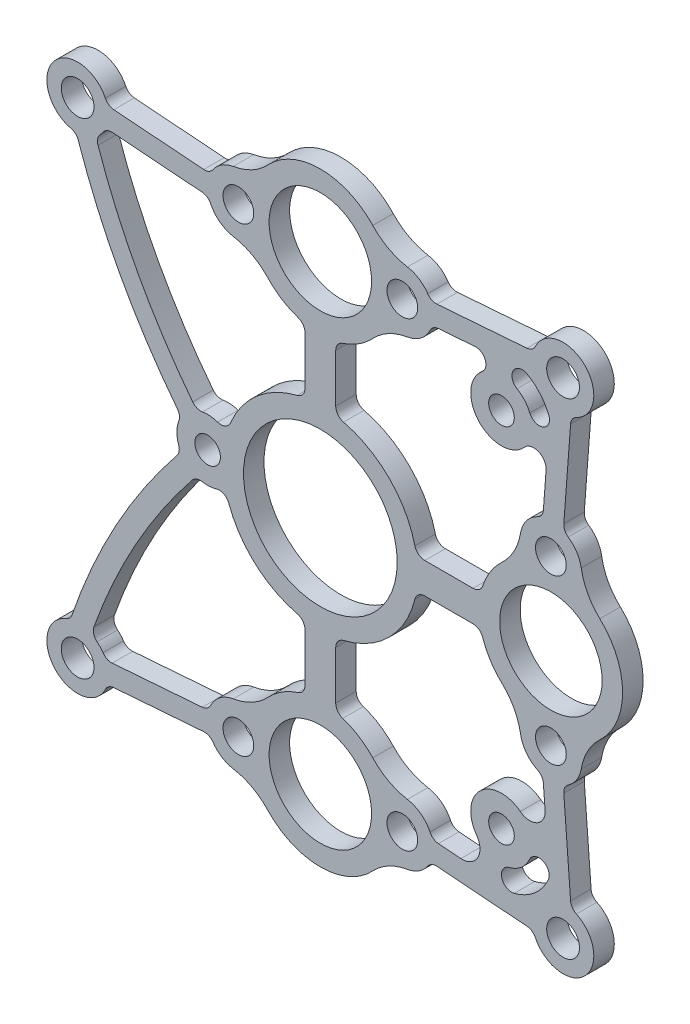
SolidWorks part; units mm, degrees
material "A2017"
ref_plane "正面" through (0, 0, 0) normal (0, 0, 1) x (1, 0, 0)
ref_plane "平面" through (0, 0, 0) normal (0, 1, 0) x (1, 0, 0)
ref_plane "右側面" through (0, 0, 0) normal (1, 0, 0) x (0, 0, -1)
sketch "ｽｹｯﾁ1" plane through (0, 0, 0) normal (0, 0, 1) x (1, 0, 0)
  line L0 (0, 29.5) -> (0, 22.5) construction
  line L1 (-8, 22.5) -> (8, 22.5) construction
  line L2 (29.5, 0) -> (22.5, 0) construction
  line L3 (22.5, 8) -> (22.5, -8) construction
  line L4 (0, -29.5) -> (0, -22.5) construction
  line L5 (8, -22.5) -> (-8, -22.5) construction
  line L6 (-29.5, 0) -> (-22.5, 0) construction
  line L7 (-22.5, -8) -> (-22.5, 8) construction
  circle A1 centre (23.6881, 23.6881) radius 3
  circle A2 centre (23.6881, 23.6881) radius 3
  circle A3 centre (22.5, 0) radius 5
  circle A5 centre (22.5, -8) radius 1.5
  circle A7 centre (0, 22.5) radius 5
  circle A8 centre (0, 22.5) radius 5
  circle A9 centre (0, 0) radius 7.5
  circle A10 centre (0, 0) radius 7.5
  circle A11 centre (8, 22.5) radius 1.5
  circle A12 centre (8, 22.5) radius 1.5
  circle A13 centre (-8, 22.5) radius 1.5
  circle A14 centre (-8, 22.5) radius 1.5
  circle A15 centre (-23.6881, -23.6881) radius 3
  circle A16 centre (-23.6881, -23.6881) radius 3
  circle A17 centre (-23.6881, 23.6881) radius 3
  circle A18 centre (-23.6881, 23.6881) radius 3
  circle A19 centre (23.6881, -23.6881) radius 3
  circle A20 centre (23.6881, -23.6881) radius 3
  circle A21 centre (22.5, 8) radius 1.5
  arc A23 (27.2784, 5.1154) -> (27.2784, -5.1154) centre (22.5, 0) cw
  arc A25 (27.2784, 5.1154) -> (25.458, 8.5) centre (31.3741, 9.5) cw
  arc A27 (27.2784, -5.1154) -> (25.458, -8.5) centre (31.3741, -9.5) ccw
  circle A42 centre (0, 0) radius 9.5
  circle A43 centre (-23.6881, 23.6881) radius 1.6
  circle A44 centre (-23.6881, -23.6881) radius 1.6
  circle A45 centre (23.6881, -23.6881) radius 1.6
  circle A46 centre (23.6881, 23.6881) radius 1.6
  circle A47 centre (-8, 22.5) radius 3 construction
  circle A48 centre (0, 22.5) radius 7 construction
  circle A49 centre (8, 22.5) radius 3 construction
  arc A50 (-5.1154, 27.2784) -> (5.1154, 27.2784) centre (0, 22.5) cw
  arc A51 (-5.1154, 27.2784) -> (-8.5, 25.458) centre (-9.5, 31.3741) cw
  arc A52 (5.1154, 27.2784) -> (8.5, 25.458) centre (9.5, 31.3741) ccw
  arc A53 (-8.5, 25.458) -> (-8.5, 19.542) centre (-8, 22.5) ccw
  arc A54 (8.5, 25.458) -> (8.5, 19.542) centre (8, 22.5) cw
  arc A55 (-5.1154, 17.7216) -> (-8.5, 19.542) centre (-9.5, 13.6259) ccw
  arc A56 (-5.1154, 17.7216) -> (5.1154, 17.7216) centre (0, 22.5) ccw
  arc A57 (5.1154, 17.7216) -> (8.5, 19.542) centre (9.5, 13.6259) cw
  arc A58 (25.458, 8.5) -> (19.542, 8.5) centre (22.5, 8) ccw
  arc A59 (25.458, -8.5) -> (19.542, -8.5) centre (22.5, -8) cw
  arc A60 (17.7216, 5.1154) -> (19.542, 8.5) centre (13.6259, 9.5) ccw
  arc A61 (17.7216, 5.1154) -> (17.7216, -5.1154) centre (22.5, 0) ccw
  arc A62 (17.7216, -5.1154) -> (19.542, -8.5) centre (13.6259, -9.5) cw
  circle A63 centre (22.5, 8) radius 3 construction
  circle A64 centre (22.5, 0) radius 7 construction
  circle A65 centre (22.5, -8) radius 3 construction
  circle A66 centre (0, -22.5) radius 5
  circle A67 centre (-8, -22.5) radius 1.5
  circle A68 centre (8, -22.5) radius 1.5
  arc A69 (5.1154, -27.2784) -> (-5.1154, -27.2784) centre (0, -22.5) cw
  arc A70 (5.1154, -27.2784) -> (8.5, -25.458) centre (9.5, -31.3741) cw
  arc A71 (-5.1154, -27.2784) -> (-8.5, -25.458) centre (-9.5, -31.3741) ccw
  arc A72 (8.5, -25.458) -> (8.5, -19.542) centre (8, -22.5) ccw
  arc A73 (-8.5, -25.458) -> (-8.5, -19.542) centre (-8, -22.5) cw
  arc A74 (5.1154, -17.7216) -> (8.5, -19.542) centre (9.5, -13.6259) ccw
  arc A75 (5.1154, -17.7216) -> (-5.1154, -17.7216) centre (0, -22.5) ccw
  arc A76 (-5.1154, -17.7216) -> (-8.5, -19.542) centre (-9.5, -13.6259) cw
  circle A77 centre (8, -22.5) radius 3 construction
  circle A78 centre (0, -22.5) radius 7 construction
  circle A79 centre (-8, -22.5) radius 3 construction
  circle A80 centre (-22.5, 0) radius 5 [skipped]
  circle A81 centre (-22.5, 8) radius 1.5 [skipped]
  circle A82 centre (-22.5, -8) radius 1.5 [skipped]
  arc A83 (-27.2784, -5.1154) -> (-27.2784, 5.1154) centre (-22.5, 0) cw [skipped]
  arc A84 (-27.2784, -5.1154) -> (-25.458, -8.5) centre (-31.3741, -9.5) cw [skipped]
  arc A85 (-27.2784, 5.1154) -> (-25.458, 8.5) centre (-31.3741, 9.5) ccw [skipped]
  arc A86 (-25.458, -8.5) -> (-19.542, -8.5) centre (-22.5, -8) ccw [skipped]
  arc A87 (-25.458, 8.5) -> (-19.542, 8.5) centre (-22.5, 8) cw [skipped]
  arc A88 (-17.7216, -5.1154) -> (-19.542, -8.5) centre (-13.6259, -9.5) ccw [skipped]
  arc A89 (-17.7216, -5.1154) -> (-17.7216, 5.1154) centre (-22.5, 0) ccw [skipped]
  arc A90 (-17.7216, 5.1154) -> (-19.542, 8.5) centre (-13.6259, 9.5) cw [skipped]
  circle A91 centre (-22.5, -8) radius 3 construction
  circle A92 centre (-22.5, 0) radius 7 construction
  circle A93 centre (-22.5, 8) radius 3 construction
  point P121 (0, 0)
  dimension "D15" = 19
  dimension "D16" = 2
  dimension "D17" = 3.2
  dimension "D18" = 14
  dimension "D19" = 6
  dimension "D20" = 6
  dimension "D1" = 0
  dimension "D3" = 4
  dimension "D4" = 0
  dimension "D5" = 0
  dimension "D6" = 0
  dimension "D7" = 0
  dimension "D8" = 0
  dimension "D9" = 0
  dimension "D10" = 0
extrude "ﾎﾞｽ - 押し出し1" add sketch "ｽｹｯﾁ1" against normal blind 2
sketch "ｽｹｯﾁ2" plane through (0, 0, 0) normal (0, 0, 1) x (1, 0, 0)
  circle A0 centre (-11, 0.25) radius 1.5 construction
  circle A1 centre (17.6777, 17.9277) radius 1.5 construction
  circle A2 centre (17.6777, -17.4277) radius 1.5 construction
  circle A3 centre (-11, 0.25) radius 3
  circle A4 centre (17.6777, 17.9277) radius 3
  circle A5 centre (17.6777, -17.4277) radius 3
  dimension "D1" = 3
  dimension "D2" = 6
extrude "ﾎﾞｽ - 押し出し2" add sketch "ｽｹｯﾁ2" against normal through all
hole_wizard "M3 ねじ穴1" positions "ｽｹｯﾁ3" profile "ｽｹｯﾁ4" tap size "M3" standard "JIS" end condition through all
sketch "ｽｹｯﾁ3" plane through (0, 0, 0) normal (0, 0, 1) x (1, 0, 0)
  point P0 (-11, 0.25)
  point P3 (17.6777, 17.9277)
  point P6 (17.6777, -17.4277)
sketch "ｽｹｯﾁ4" plane through (-11, 0.25, 0) normal (1, 0, 0) x (0, -1, 0)
  line L0 (0, 0) -> (0, 2)
  line L1 (0, 2) -> (1.25, 2)
  line L2 (1.25, 2) -> (1.25, 0)
  line L5 (1.25, 0) -> (0, 0)
  line L11 (0, -6.35) -> (0, 107.95) construction
  dimension "次ｻｰﾌｪｽまでのねじ下穴ﾄﾞﾘﾙ直径" = 2.5
  dimension "次ｻｰﾌｪｽまでのねじ下穴ﾄﾞﾘﾙの深さ" = 2
cosmetic thread "穴のねじ山1" parameters "D2"=3
cosmetic thread "穴のねじ山2" parameters "D2"=3
cosmetic thread "穴のねじ山3" parameters "D2"=3
sketch "ｽｹｯﾁ5" plane through (0, 0, 0) normal (0, 0, 1) x (1, 0, 0)
  line L0 (0, 22.5) -> (0, 0) construction
  line L1 (0, 22.5) -> (0, 0) construction
  line L2 (1.5, 22.5) -> (1.5, 0)
  line L3 (-1.5, 22.5) -> (-1.5, 0)
  line L4 (22.5, 0) -> (0, 0) construction
  line L5 (22.5, -1.5) -> (0, -1.5)
  line L6 (22.5, 1.5) -> (0, 1.5)
  line L7 (0, 0) -> (0, -22.5) construction
  line L8 (1.5, 0) -> (1.5, -22.5)
  line L9 (-1.5, 0) -> (-1.5, -22.5)
  arc A0 (1.5, 22.5) -> (-1.5, 22.5) centre (0, 22.5) ccw
  arc A1 (-1.5, 0) -> (1.5, 0) centre (0, 0) ccw
  arc A2 (22.5, -1.5) -> (22.5, 1.5) centre (22.5, 0) ccw
  arc A3 (0, 1.5) -> (0, -1.5) centre (0, 0) ccw
  arc A4 (1.5, 0) -> (-1.5, 0) centre (0, 0) ccw
  arc A5 (-1.5, -22.5) -> (1.5, -22.5) centre (0, -22.5) ccw
  arc A6 (5.1154, -17.7216) -> (-5.1154, -17.7216) centre (0, -22.5) ccw construction
  arc A7 (17.7216, 5.1154) -> (17.7216, -5.1154) centre (22.5, 0) ccw construction
  arc A8 (-5.1154, 17.7216) -> (5.1154, 17.7216) centre (0, 22.5) ccw construction
  arc A9 (-9.2456, -2.1836) -> (-9.1369, 2.6014) centre (0, 0) ccw construction
  arc A10 (5.1154, -17.7216) -> (-5.1154, -17.7216) centre (0, -22.5) ccw
  arc A11 (17.7216, 5.1154) -> (17.7216, -5.1154) centre (22.5, 0) ccw
  arc A12 (-5.1154, 17.7216) -> (5.1154, 17.7216) centre (0, 22.5) ccw
  arc A13 (-9.2456, -2.1836) -> (-9.1369, 2.6014) centre (0, 0) ccw
  point P4 (0, 11.25)
  point P12 (11.25, 0)
  point P17 (0, -11.25)
  arc M19 (-5.1154, 17.7216) -> (5.1154, 17.7216) centre (0, 22.5) ccw
  dimension "D1" = 3
extrude "ﾎﾞｽ - 押し出し3" add sketch "ｽｹｯﾁ5" against normal through all contours A13 L2 L3 M19 | A13 L5 A11 L6 | A13 L9 A10 L8 region at (0, 12.5073, 0) region at (12.5073, 0, 0) region at (0, -12.5073, 0)
sketch "ｽｹｯﾁ6" plane through (0, 0, 0) normal (0, 0, 1) x (1, 0, 0)
  line L0 (8, 22.5) -> (23.6881, 23.6881) construction
  line L1 (7.9245, 23.4971) -> (23.6126, 24.6852)
  line L2 (8.0755, 21.5029) -> (23.7636, 22.6909)
  line L3 (22.5, 8) -> (23.6881, 23.6881) construction
  line L4 (21.5029, 8.0755) -> (22.6909, 23.7636)
  line L5 (23.4971, 7.9245) -> (24.6852, 23.6126)
  line L6 (0, 0) -> (29.5, 0) construction
  line L7 (8, -22.5) -> (23.6881, -23.6881) construction
  line L8 (7.9245, -23.4971) -> (23.6126, -24.6852)
  line L9 (8.0755, -21.5029) -> (23.7636, -22.6909)
  line L10 (22.5, -8) -> (23.6881, -23.6881) construction
  line L11 (21.5029, -8.0755) -> (22.6909, -23.7636)
  line L12 (23.4971, -7.9245) -> (24.6852, -23.6126)
  arc A0 (7.9245, 23.4971) -> (8.0755, 21.5029) centre (8, 22.5) ccw
  arc A1 (23.7636, 22.6909) -> (23.6126, 24.6852) centre (23.6881, 23.6881) ccw
  arc A2 (21.5029, 8.0755) -> (23.4971, 7.9245) centre (22.5, 8) ccw
  arc A3 (24.6852, 23.6126) -> (22.6909, 23.7636) centre (23.6881, 23.6881) ccw
  arc A5 (8.5, 19.542) -> (8.5, 25.458) centre (8, 22.5) ccw construction
  arc A6 (25.458, 8.5) -> (19.542, 8.5) centre (22.5, 8) ccw construction
  circle A7 centre (23.6881, 23.6881) radius 3 construction
  arc A8 (8.5, 19.542) -> (8.5, 25.458) centre (8, 22.5) ccw
  arc A9 (25.458, 8.5) -> (19.542, 8.5) centre (22.5, 8) ccw
  circle A10 centre (23.6881, 23.6881) radius 3
  arc A11 (7.9245, -23.4971) -> (8.0755, -21.5029) centre (8, -22.5) cw
  arc A12 (23.7636, -22.6909) -> (23.6126, -24.6852) centre (23.6881, -23.6881) cw
  arc A13 (21.5029, -8.0755) -> (23.4971, -7.9245) centre (22.5, -8) cw
  arc A14 (24.6852, -23.6126) -> (22.6909, -23.7636) centre (23.6881, -23.6881) cw
  circle A15 centre (23.6881, -23.6881) radius 3
  arc A16 (25.458, -8.5) -> (19.542, -8.5) centre (22.5, -8) cw
  arc A17 (8.5, -19.542) -> (8.5, -25.458) centre (8, -22.5) cw
  arc A18 (27.2784, -5.1154) -> (27.2784, 5.1154) centre (22.5, 0) ccw construction
  point P4 (15.844, 23.094)
  point P12 (23.094, 15.844)
  point P33 (15.844, -23.094)
  point P40 (23.094, -15.844)
  circle M10 centre (23.6881, 23.6881) radius 3
  dimension "D1" = 2
extrude "ﾎﾞｽ - 押し出し4" add sketch "ｽｹｯﾁ6" against normal through all contours L12 A16 L11 A15 | L9 A17 L8 A15 | A9 L5 L4 M10 | A8 L2 L1 M10 region at (15.844, 23.094, 0) region at (23.094, 15.844, 0) region at (15.844, -23.094, 0) region at (23.094, -15.844, 0)
sketch "ｽｹｯﾁ7" plane through (0, 0, 0) normal (0, 0, 1) x (1, 0, 0)
  line L0 (10.8959, 21.7164) -> (20.9432, 22.4773) construction
  line L1 (23.6881, 23.6881) -> (17.6777, 17.9277) construction
  line L2 (21.7164, 10.8959) -> (22.4773, 20.9432) construction
  line L3 (20.823, 15.1286) -> (17.6777, 17.9277) construction
  line L4 (17.6777, 17.9277) -> (15.1608, 21.0366) construction
  line L5 (15.1608, 21.0366) -> (20.823, 15.1286) construction
  line L6 (21.7164, 10.8959) -> (22.4773, 20.9432)
  line L7 (10.8959, 21.7164) -> (20.9432, 22.4773)
  line L8 (17.6777, -17.4277) -> (23.6881, -23.6881) construction
  line L9 (10.8959, -21.7164) -> (20.9432, -22.4773) construction
  line L10 (21.7164, -10.8959) -> (22.4773, -20.9432) construction
  line L11 (10.8959, -21.7164) -> (20.9432, -22.4773)
  line L12 (21.7164, -10.8959) -> (22.4773, -20.9432)
  line L13 (13.845, -20.2029) -> (17.6777, -17.4277) construction
  line L14 (17.6777, -17.4277) -> (20.4376, -13.8734) construction
  line L15 (20.4376, -13.8734) -> (13.845, -20.2029) construction
  circle A0 centre (15.1608, 21.0366) radius 1
  circle A1 centre (17.6777, 17.9277) radius 3 construction
  circle A2 centre (17.6777, 17.9277) radius 3
  circle A3 centre (20.823, 15.1286) radius 1.2105
  arc A4 (20.9432, 22.4773) -> (22.4773, 20.9432) centre (23.6881, 23.6881) ccw construction
  arc A5 (20.9432, 22.4773) -> (22.4773, 20.9432) centre (23.6881, 23.6881) ccw
  arc A6 (22.4773, -20.9432) -> (20.9432, -22.4773) centre (23.6881, -23.6881) ccw construction
  circle A7 centre (17.6777, -17.4277) radius 3 construction
  arc A8 (22.4773, -20.9432) -> (20.9432, -22.4773) centre (23.6881, -23.6881) ccw
  circle A9 centre (17.6777, -17.4277) radius 3
  circle A10 centre (20.4376, -13.8734) radius 1.5
  circle A11 centre (13.845, -20.2029) radius 1.732
  dimension "D1" = 2
  dimension "D2" = 3
extrude "ﾎﾞｽ - 押し出し5" add sketch "ｽｹｯﾁ7" against normal through all contours A11 L11 A8 L12 A10 A9 | A5 L7 A0 A2 A3 L6 region at (20.1419, 20.0544, 0) region at (19.7084, -19.7916, 0)
sketch "ｽｹｯﾁ8" plane through (0, 0, 0) normal (0, 0, 1) x (1, 0, 0)
  line L0 (-8, 22.5) -> (-23.6881, 23.6881) construction
  line L1 (-8.0755, 21.5029) -> (-23.7636, 22.6909)
  line L2 (-7.9245, 23.4971) -> (-23.6126, 24.6852)
  line L3 (-8, -22.5) -> (-23.6881, -23.6881) construction
  line L4 (-7.9245, -23.4971) -> (-23.6126, -24.6852)
  line L5 (-8.0755, -21.5029) -> (-23.7636, -22.6909)
  line L6 (-11, 0.25) -> (22.5, 0) construction
  line L18 (10.7448, -23.7107) -> (20.7922, -24.4716)
  line L19 (24.4716, -20.7922) -> (23.7107, -10.7448)
  line L20 (23.7107, 10.7448) -> (24.4716, 20.7922)
  line L21 (20.7922, 24.4716) -> (10.7448, 23.7107)
  line L22 (-1.5, 15.6626) -> (-1.5, 9.3808)
  line L23 (-1.5, -9.3808) -> (-1.5, -15.6626)
  line L24 (10.7448, -23.7107) -> (20.7922, -24.4716)
  line L25 (24.4716, -20.7922) -> (23.7107, -10.7448)
  line L26 (23.7107, 10.7448) -> (24.4716, 20.7922)
  line L27 (20.7922, 24.4716) -> (10.7448, 23.7107)
  line L28 (-1.5, 15.6626) -> (-1.5, 9.3808)
  line L29 (-1.5, -9.3808) -> (-1.5, -15.6626)
  arc A0 (-8.0755, 21.5029) -> (-7.9245, 23.4971) centre (-8, 22.5) ccw
  arc A1 (-23.6126, 24.6852) -> (-23.7636, 22.6909) centre (-23.6881, 23.6881) ccw
  arc A2 (-7.9245, -23.4971) -> (-8.0755, -21.5029) centre (-8, -22.5) ccw
  arc A3 (-23.7636, -22.6909) -> (-23.6126, -24.6852) centre (-23.6881, -23.6881) ccw
  arc A8 (-23.6881, 23.6881) -> (-11, 0.25) centre (34.1027, 39.8195) ccw construction
  circle A9 centre (-23.6881, -23.6881) radius 3 construction
  circle A10 centre (-23.6881, 23.6881) radius 3 construction
  circle A11 centre (-23.6881, -23.6881) radius 3
  circle A12 centre (-23.6881, 23.6881) radius 3
  arc A13 (-24.6513, 23.4192) -> (-11.7517, -0.4095) centre (34.1027, 39.8195) ccw
  arc A14 (-22.7249, 23.9569) -> (-10.2483, 0.9095) centre (34.1027, 39.8195) ccw
  arc A15 (-22.7249, 23.9569) -> (-24.6513, 23.4192) centre (-23.6881, 23.6881) ccw
  arc A16 (-11.7517, -0.4095) -> (-10.2483, 0.9095) centre (-11, 0.25) ccw
  arc A17 (-24.0365, -22.9961) -> (-11, 0.25) centre (33.5072, -39.9882) cw construction
  arc A18 (-24.9955, -22.7129) -> (-11.7418, 0.9206) centre (33.5072, -39.9882) cw
  arc A19 (-23.0774, -23.2793) -> (-10.2582, -0.4206) centre (33.5072, -39.9882) cw
  arc A20 (-23.0774, -23.2793) -> (-24.9955, -22.7129) centre (-24.0365, -22.9961) cw
  arc A21 (-11.7418, 0.9206) -> (-10.2582, -0.4206) centre (-11, 0.25) cw
  arc A33 (8.5, -25.458) -> (10.7448, -23.7107) centre (8, -22.5) ccw
  arc A34 (20.7922, -24.4716) -> (24.4716, -20.7922) centre (23.6881, -23.6881) ccw
  arc A35 (23.7107, -10.7448) -> (25.458, -8.5) centre (22.5, -8) ccw
  arc A36 (27.2784, -5.1154) -> (25.458, -8.5) centre (31.3741, -9.5) ccw
  arc A37 (27.2784, -5.1154) -> (27.2784, 5.1154) centre (22.5, 0) ccw
  arc A38 (25.458, 8.5) -> (27.2784, 5.1154) centre (31.3741, 9.5) ccw
  arc A39 (25.458, 8.5) -> (23.7107, 10.7448) centre (22.5, 8) ccw
  arc A40 (24.4716, 20.7922) -> (20.7922, 24.4716) centre (23.6881, 23.6881) ccw
  arc A41 (10.7448, 23.7107) -> (8.5, 25.458) centre (8, 22.5) ccw
  arc A42 (5.1154, 27.2784) -> (8.5, 25.458) centre (9.5, 31.3741) ccw
  arc A43 (5.1154, 27.2784) -> (-5.1154, 27.2784) centre (0, 22.5) ccw
  arc A44 (-8.5, 25.458) -> (-5.1154, 27.2784) centre (-9.5, 31.3741) ccw
  arc A45 (-8.5, 25.458) -> (-8.5, 19.542) centre (-8, 22.5) ccw
  arc A46 (-5.1154, 17.7216) -> (-8.5, 19.542) centre (-9.5, 13.6259) ccw
  arc A47 (-5.1154, 17.7216) -> (-1.5, 15.6626) centre (0, 22.5) ccw
  arc A48 (-1.5, 9.3808) -> (-9.1369, 2.6014) centre (0, 0) ccw
  arc A49 (-9.1369, 2.6014) -> (-9.2456, -2.1836) centre (-11, 0.25) ccw
  arc A50 (-9.2456, -2.1836) -> (-1.5, -9.3808) centre (0, 0) ccw
  arc A51 (-1.5, -15.6626) -> (-5.1154, -17.7216) centre (0, -22.5) ccw
  arc A52 (-8.5, -19.542) -> (-5.1154, -17.7216) centre (-9.5, -13.6259) ccw
  arc A53 (-8.5, -19.542) -> (-8.5, -25.458) centre (-8, -22.5) ccw
  arc A54 (-5.1154, -27.2784) -> (-8.5, -25.458) centre (-9.5, -31.3741) ccw
  arc A55 (-5.1154, -27.2784) -> (5.1154, -27.2784) centre (0, -22.5) ccw
  arc A56 (8.5, -25.458) -> (5.1154, -27.2784) centre (9.5, -31.3741) ccw
  arc A57 (8.5, -25.458) -> (10.7448, -23.7107) centre (8, -22.5) ccw
  arc A58 (20.7922, -24.4716) -> (24.4716, -20.7922) centre (23.6881, -23.6881) ccw
  arc A59 (23.7107, -10.7448) -> (25.458, -8.5) centre (22.5, -8) ccw
  arc A60 (27.2784, -5.1154) -> (25.458, -8.5) centre (31.3741, -9.5) ccw
  arc A61 (27.2784, -5.1154) -> (27.2784, 5.1154) centre (22.5, 0) ccw
  arc A62 (25.458, 8.5) -> (27.2784, 5.1154) centre (31.3741, 9.5) ccw
  arc A63 (25.458, 8.5) -> (23.7107, 10.7448) centre (22.5, 8) ccw
  arc A64 (24.4716, 20.7922) -> (20.7922, 24.4716) centre (23.6881, 23.6881) ccw
  arc A65 (10.7448, 23.7107) -> (8.5, 25.458) centre (8, 22.5) ccw
  arc A66 (5.1154, 27.2784) -> (8.5, 25.458) centre (9.5, 31.3741) ccw
  arc A67 (5.1154, 27.2784) -> (-5.1154, 27.2784) centre (0, 22.5) ccw
  arc A68 (-8.5, 25.458) -> (-5.1154, 27.2784) centre (-9.5, 31.3741) ccw
  arc A69 (-8.5, 25.458) -> (-8.5, 19.542) centre (-8, 22.5) ccw
  arc A70 (-5.1154, 17.7216) -> (-8.5, 19.542) centre (-9.5, 13.6259) ccw
  arc A71 (-5.1154, 17.7216) -> (-1.5, 15.6626) centre (0, 22.5) ccw
  arc A72 (-1.5, 9.3808) -> (-9.1369, 2.6014) centre (0, 0) ccw
  arc A73 (-9.1369, 2.6014) -> (-9.2456, -2.1836) centre (-11, 0.25) ccw
  arc A74 (-9.2456, -2.1836) -> (-1.5, -9.3808) centre (0, 0) ccw
  arc A75 (-1.5, -15.6626) -> (-5.1154, -17.7216) centre (0, -22.5) ccw
  arc A76 (-8.5, -19.542) -> (-5.1154, -17.7216) centre (-9.5, -13.6259) ccw
  arc A77 (-8.5, -19.542) -> (-8.5, -25.458) centre (-8, -22.5) ccw
  arc A78 (-5.1154, -27.2784) -> (-8.5, -25.458) centre (-9.5, -31.3741) ccw
  arc A79 (-5.1154, -27.2784) -> (5.1154, -27.2784) centre (0, -22.5) ccw
  arc A80 (8.5, -25.458) -> (5.1154, -27.2784) centre (9.5, -31.3741) ccw
  point P4 (-15.844, 23.094)
  point P9 (-15.844, -23.094)
  point P18 (-18.6619, 11.2556)
  point P27 (-18.8253, -10.64)
  dimension "D3" = 60
  dimension "D1" = 2
  dimension "D2" = 0
extrude "ﾎﾞｽ - 押し出し6" add sketch "ｽｹｯﾁ8" against normal through all contours A73 A12 | A69 L2 A12 L1 | A73 A14 A11 | A77 L5 A11 L4 region at (-15.844, 23.094, 0) region at (-18.3988, 11.398, 0) region at (-18.6986, -11.0584, 0) region at (-15.844, -23.094, 0)
sketch "ｽｹｯﾁ9" plane through (0, 0, 0) normal (0, 0, 1) x (1, 0, 0)
  line L0 (10.8959, 21.7164) -> (15.0853, 22.0337) construction
  line L1 (15.0853, 22.0337) -> (22.603, 22.603) construction
  line L2 (22.603, 22.603) -> (22.0198, 14.9011) construction
  line L3 (21.7164, 10.8959) -> (22.0301, 15.0372) construction
  line L4 (22.0198, 14.9011) -> (21.7164, 10.8959) construction
  line L5 (13.7142, -21.9299) -> (22.603, -22.603) construction
  line L6 (22.603, -22.603) -> (21.9334, -13.7602) construction
  line L7 (21.7164, -10.8959) -> (21.9334, -13.7602) construction
  line L8 (10.8959, -21.7164) -> (13.7142, -21.9299) construction
  arc A0 (19.6977, 21.3802) -> (21.3638, 19.4811) centre (17.6777, 17.9277) cw construction
  arc A1 (22.2853, 19.8694) -> (20.2027, 22.2433) centre (17.6777, 17.9277) ccw
  arc A2 (20.4422, 19.0927) -> (19.1927, 20.517) centre (17.6777, 17.9277) ccw
  arc A3 (20.4422, 19.0927) -> (22.2853, 19.8694) centre (21.3638, 19.4811) ccw
  arc A4 (20.2027, 22.2433) -> (19.1927, 20.517) centre (19.6977, 21.3802) ccw
  circle A5 centre (17.6777, 17.9277) radius 3 construction
  circle A6 centre (17.6777, -17.4277) radius 3 construction
  arc A7 (21.3315, -19.0555) -> (18.671, -21.3024) centre (17.6777, -17.4277) cw construction
  arc A8 (18.9193, -22.2711) -> (22.245, -19.4624) centre (17.6777, -17.4277) ccw
  arc A9 (18.4227, -20.3337) -> (20.4181, -18.6485) centre (17.6777, -17.4277) ccw
  arc A10 (18.4227, -20.3337) -> (18.9193, -22.2711) centre (18.671, -21.3024) ccw
  arc A11 (22.245, -19.4624) -> (20.4181, -18.6485) centre (21.3315, -19.0555) ccw
  point P4 (20.6846, 20.5656)
  point P37 (20.2586, -20.4837)
  dimension "D1" = 2
  dimension "D2" = 2
extrude "ｶｯﾄ - 押し出し1" cut sketch "ｽｹｯﾁ9" against normal up to surface (2 mm away) up to face at (-10.4688, -14.7595, -2)
fillet "ﾌｨﾚｯﾄ1" radius 1 42 edges at (1.5, -15.6626, -1) (1.5, -9.3808, -1) (9.3808, -1.5, -1) (15.6626, -1.5, -1) (21.7164, -10.8959, -1) (10.8959, -21.7164, -1) (21.7164, 10.8959, -1) (15.6626, 1.5, -1) (9.3808, 1.5, -1) (1.5, 9.3808, -1) (1.5, 15.6626, -1) (10.8959, 21.7164, -1) (-20.7922, -24.4716, -1) (-10.7448, -23.7107, -1) (10.7448, -23.7107, -1) (20.7922, -24.4716, -1) (24.4716, -20.7922, -1) (23.7107, -10.7448, -1) (23.7107, 10.7448, -1) (24.4716, 20.7922, -1) (20.7922, 24.4716, -1) (10.7448, 23.7107, -1) (-10.7448, 23.7107, -1) (-23.8205, 20.691, -1) (-13.5819, 1.7777, -1) (-13.6044, -1.239, -1) (-24.3865, -20.7705, -1) (-1.5, 15.6626, -1) (-1.5, 9.3808, -1) (-9.1369, 2.6014, -1) (-12.0474, 3.0612, -1) (-21.9068, 21.2741, -1) (-20.9432, 22.4773, -1) (-10.8959, 21.7164, -1) (-22.3541, -21.001, -1) (-12.0892, -2.5453, -1) (-9.2456, -2.1836, -1) (-1.5, -9.3808, -1) (-1.5, -15.6626, -1) (-10.8959, -21.7164, -1) (-20.9432, -22.4773, -1) (-20.7922, 24.4716, -1)
